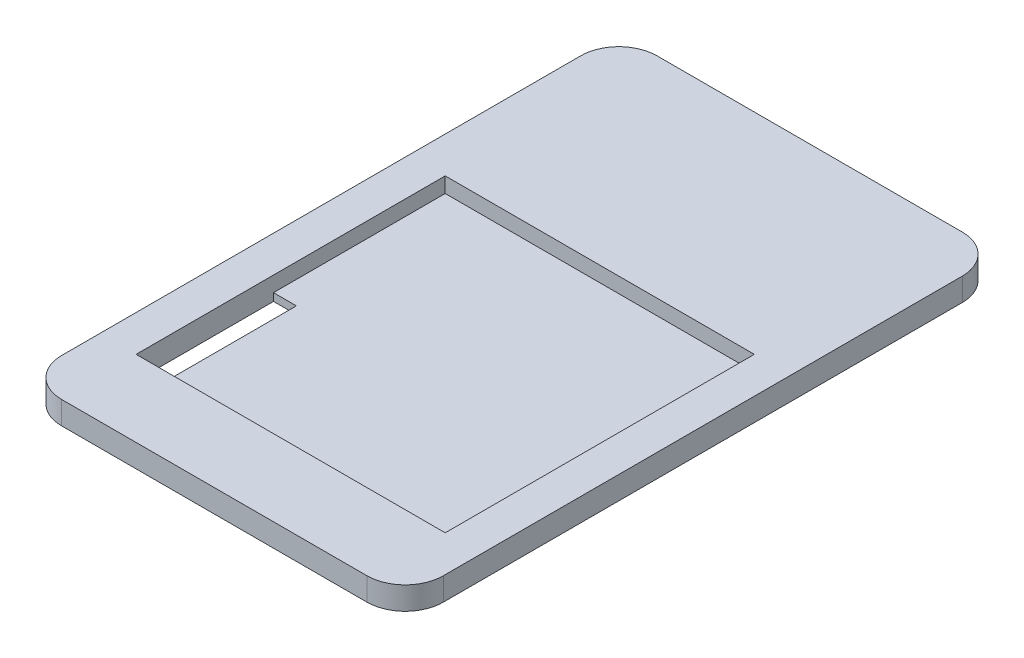
SolidWorks part; units mm, degrees
material "PMMA"
ref_plane "Front Plane" through (0, 0, 0) normal (0, 0, 1) x (1, 0, 0)
ref_plane "Top Plane" through (0, 0, 0) normal (0, 1, 0) x (1, 0, 0)
ref_plane "Right Plane" through (0, 0, 0) normal (1, 0, 0) x (0, 0, -1)
sketch "Sketch1" plane through (0, 0, 0) normal (0, 1, 0) x (1, 0, 0)
  line L0 (0, 51.4541) -> (0, -51.759) construction
  line L1 (-52.1402, 0) -> (52.1402, 0) construction
  line L2 (-20.25, -11) -> (-17.25, -11)
  line L3 (-25, -39) -> (25, -39)
  line L4 (-25, -39) -> (-25, 39)
  line L5 (-25, 39) -> (25, 39)
  line L6 (25, -39) -> (25, 39)
  line L7 (-25, -39) -> (25, 39) construction
  line L8 (-25, 39) -> (25, -39) construction
  line L9 (-20.25, -29) -> (20.25, -29)
  line L10 (-20.25, -29) -> (-20.25, 11.5)
  line L11 (-20.25, 11.5) -> (20.25, 11.5)
  line L12 (20.25, -29) -> (20.25, 11.5)
  line L13 (-20.25, -29) -> (20.25, 11.5) construction
  line L14 (-20.25, 11.5) -> (20.25, -29) construction
  line L15 (-17.25, -11) -> (-17.25, -27)
  line L16 (-17.25, -27) -> (-20.25, -27)
  point P5 (0, 0)
  point P11 (0, -8.75)
  dimension "D1" = 78
  dimension "D2" = 50
  dimension "D3" = 40.5
  dimension "D4" = 40.5
  dimension "D5" = 10
  dimension "D6" = 2
  dimension "D7" = 3
  dimension "D8" = 16
extrude "Boss-Extrude1" add sketch "Sketch1" along normal blind 3 contours L3 L6 L5 L4 L12 L9 L10 L11 region at (-24.0735, 0, 0)
extrude "Boss-Extrude2" add sketch "Sketch1<3>" along normal blind 1 contours L15 L16 L10 L9 L12 L11 L2 region at (0.5652, 0, 8.441)
sketch "Sketch1<3>" plane through (0, 0, 0) normal (0, 1, 0) x (1, 0, 0) same geometry as "Sketch1"
fillet "Fillet1" radius 5 4 edges at (-25, 1.5, 39) (25, 1.5, 39) (25, 1.5, -39) (-25, 1.5, -39)
